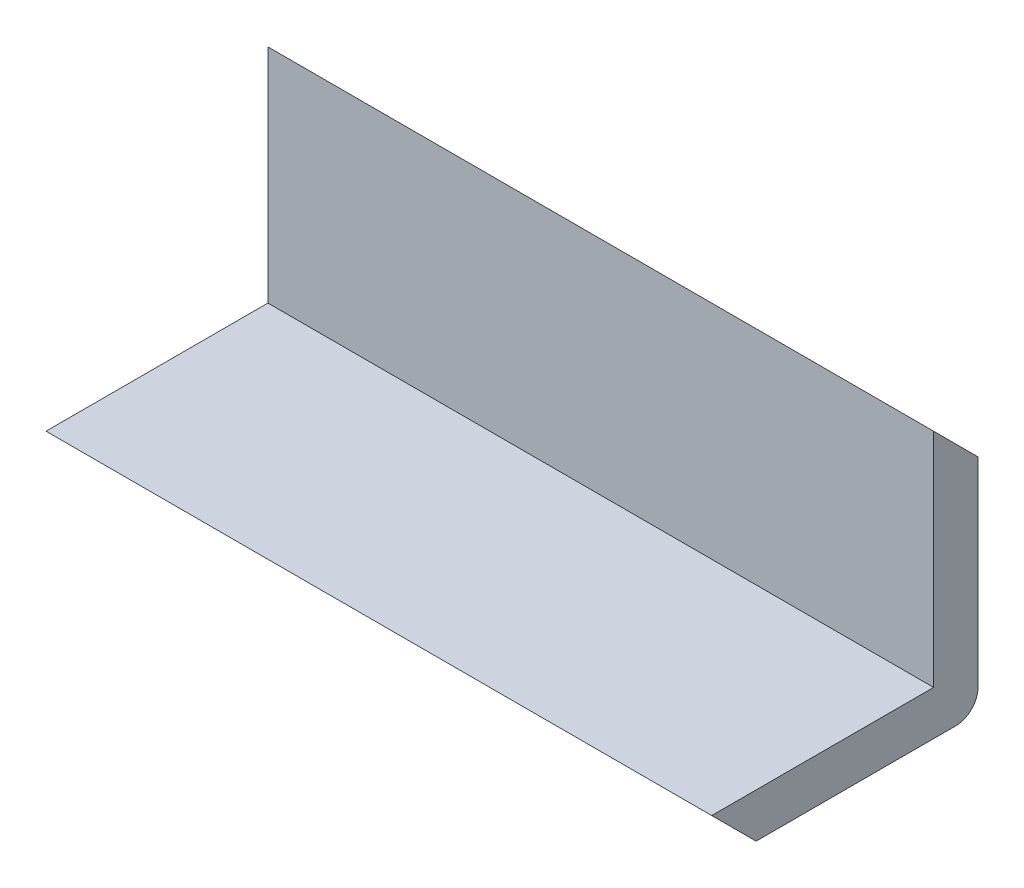
SolidWorks part; units mm, degrees
ref_plane "Alzado" through (0, 0, 0) normal (0, 0, 1) x (1, 0, 0)
ref_plane "Planta" through (0, 0, 0) normal (0, 1, 0) x (1, 0, 0)
ref_plane "Vista lateral" through (0, 0, 0) normal (1, 0, 0) x (0, 0, -1)
sketch "Croquis1" plane through (0, 0, 0) normal (0, 1, 0) x (1, 0, 0)
  line L1 (-15, -5) -> (15, -5)
  line L2 (-15, -5) -> (-15, 5)
  line L3 (-15, 5) -> (15, 5)
  line L4 (15, -5) -> (15, 5)
  line L5 (-15, -5) -> (15, 5) construction
  line L6 (-15, 5) -> (15, -5) construction
  point P0 (0, 0)
extrude "Saliente-Extruir1" add sketch "Croquis1" along normal blind 2
sketch "Croquis2" plane through (0, 2, 0) normal (0, 1, 0) x (1, 0, 0)
  line L1 (-15, 5) -> (15, 5)
  line L2 (-15, 5) -> (-15, 7)
  line L3 (-15, 7) -> (15, 7)
  line L4 (15, 5) -> (15, 7)
extrude "Saliente-Extruir2" add sketch "Croquis2" along normal blind 10 and the other way blind 2
sketch "Croquis3" plane through (0, 0, -7) normal (0, 0, -1) x (-1, 0, 0)
  line L0 (4.5, 1) -> (-4.5, 1)
  line L1 (0, 12) -> (0, 10)
  line L2 (-15, 12) -> (15, 12) construction
  line L3 (0, 0) -> (0, 1)
  line L4 (4.5, 10) -> (-4.5, 10)
  line L5 (-4.5, 10) -> (-4.5, 1)
  line L6 (4.5, 1) -> (4.5, 10)
  line L7 (-98.6997, -323.0785) -> (323.6455, -323.0785) construction
  line L59 (3.9233, 6.2112) -> (3.4713, 6.2112)
  line L60 (-3.544, 6.231) -> (-3.9391, 6.231)
  line L61 (-3.454, 6.321) -> (-3.454, 8.7529)
  line L62 (-3.544, 8.8429) -> (-3.9391, 8.8429)
  line L63 (-4.0291, 6.321) -> (-4.0291, 8.7529)
  line L64 (4.0262, 6.3142) -> (4.0262, 8.7461)
  line L65 (3.9233, 8.8491) -> (3.4713, 8.8491)
  line L66 (3.3683, 6.3142) -> (3.3683, 8.7461)
  line L67 (3.8801, 9.1955) -> (3.382, 9.1955)
  line L68 (4.3401, 8.7355) -> (4.3401, 6.3248)
  line L69 (2.922, 8.7355) -> (2.922, 6.3248)
  line L70 (3.8801, 5.8648) -> (3.382, 5.8648)
  line L73 (-3.4383, 9.2735) -> (-3.9364, 9.2735)
  line L74 (-2.9121, 8.7472) -> (-2.9121, 6.3366)
  line L75 (-4.4627, 8.7472) -> (-4.4627, 6.3366)
  line L76 (-3.4383, 5.8103) -> (-3.9364, 5.8103)
  line L77 (-2.5009, 7.5751) -> (-2.8056, 5.4663)
  line L78 (-2.8056, 5.4663) -> (-3.4742, 5.2275)
  line L79 (-2.1057, 7.3815) -> (-2.3528, 5.4663)
  line L80 (2.5148, 7.575) -> (2.8006, 5.4663)
  line L81 (2.8006, 5.4663) -> (3.4713, 5.2438)
  line L82 (2.122, 7.3815) -> (2.3816, 5.4663)
  line L83 (0.4179, 2.9212) -> (-0.7796, 2.9212)
  line L84 (-0.7796, 2.9212) -> (-0.1808, 4.4416)
  line L85 (-0.1808, 4.4416) -> (-1.2285, 4.4416)
  line L86 (-1.2285, 4.4416) -> (0.5995, 7.0524)
  line L87 (0.5995, 7.0524) -> (0.1139, 4.8778)
  line L88 (0.1139, 4.8778) -> (1.2557, 4.8778)
  line L89 (1.2557, 4.8778) -> (0.4179, 2.9212)
  arc A2 (-3.544, 6.231) -> (-3.454, 6.321) centre (-3.544, 6.321) ccw
  arc A3 (-3.9391, 6.231) -> (-4.0291, 6.321) centre (-3.9391, 6.321) cw
  arc A4 (-3.454, 8.7529) -> (-3.544, 8.8429) centre (-3.544, 8.7529) ccw
  arc A5 (-3.9391, 8.8429) -> (-4.0291, 8.7529) centre (-3.9391, 8.7529) ccw
  arc A6 (3.9233, 6.2112) -> (4.0262, 6.3142) centre (3.9233, 6.3142) ccw
  arc A7 (3.4713, 6.2112) -> (3.3683, 6.3142) centre (3.4713, 6.3142) cw
  arc A8 (4.0262, 8.7461) -> (3.9233, 8.8491) centre (3.9233, 8.7461) ccw
  arc A9 (3.4713, 8.8491) -> (3.3683, 8.7461) centre (3.4713, 8.7461) ccw
  arc A10 (4.3401, 8.7355) -> (3.8801, 9.1955) centre (3.8801, 8.7355) ccw
  arc A11 (3.382, 9.1955) -> (2.922, 8.7355) centre (3.382, 8.7355) ccw
  arc A12 (4.3401, 6.3248) -> (3.8801, 5.8648) centre (3.8801, 6.3248) cw
  arc A13 (2.922, 6.3248) -> (3.382, 5.8648) centre (3.382, 6.3248) ccw
  arc A14 (-2.9121, 8.7472) -> (-3.4383, 9.2735) centre (-3.4383, 8.7472) ccw
  arc A15 (-3.9364, 9.2735) -> (-4.4627, 8.7472) centre (-3.9364, 8.7472) ccw
  arc A16 (-2.9121, 6.3366) -> (-3.4383, 5.8103) centre (-3.4383, 6.3366) cw
  arc A17 (-4.4627, 6.3366) -> (-3.9364, 5.8103) centre (-3.9364, 6.3366) ccw
  arc A18 (2.122, 7.3815) -> (-2.1057, 7.3815) centre (0.0081, 4.1157) ccw
  arc A19 (2.5148, 7.575) -> (-2.5009, 7.5751) centre (0.0069, 4.6061) ccw
  arc A20 (-3.4742, 5.2275) -> (-2.1871, 1.7128) centre (2.1676, 5.3005) ccw
  arc A21 (-2.3528, 5.4663) -> (-3.0461, 4.9452) centre (-3.2171, 5.8944) cw
  arc A22 (-3.0461, 4.9452) -> (-1.966, 2.1011) centre (2.9616, 5.5996) ccw
  arc A23 (3.4713, 5.2438) -> (2.1795, 1.7128) centre (-1.8721, 5.1969) cw
  arc A24 (2.1795, 1.7128) -> (-2.1871, 1.7128) centre (-0.0038, 14.411) cw
  arc A25 (2.3816, 5.4663) -> (3.0405, 4.9452) centre (3.1099, 5.7101) ccw
  arc A26 (3.0405, 4.9452) -> (1.9684, 2.1011) centre (-2.3868, 5.367) cw
  arc A27 (1.9684, 2.1011) -> (-1.966, 2.1011) centre (0.0012, 15.034) cw
  point P10 (0, 1)
  point P13 (0, 10)
  point P17 (0, 5.5)
  point P79 (-3.454, 8.8429)
  point P82 (-4.0291, 8.8429)
  point P96 (3.0955, 6.2746)
  dimension "D1" = 0.5751
  dimension "D2" = 0.09
  dimension "D3" = 0.46
chamfer "Chaflán1" distance 2 angle 45 1 edges at (0, 12, -7)
fillet "Redondeo2" radius 1 1 edges at (0, 0, -7)
chamfer "Chaflán2" distance 2 angle 45 1 edges at (0, 0, 5)
extrude "Cortar-Extruir1" cut sketch "Croquis3" against normal blind 1.2 contours A24 A23 L81 L80 A19 L77 L78 A20 A26 A27 A22 A21 L79 A18 L82 A25 | L69 A13 L70 A12 L68 A10 L67 A11 A9 L65 A8 L64 A6 L59 A7 L66 | L89 L88 L87 L86 L85 L84 L83 | L75 A17 L76 A16 L74 A14 L73 A15 A5 L62 A4 L61 A2 L60 A3 L63 region at (-4.1798, 9.0351, -7) region at (3.093, 9.0925, -7) region at (-0.0069, 8.3941, -7) region at (-0.0533, 4.4708, -7)
